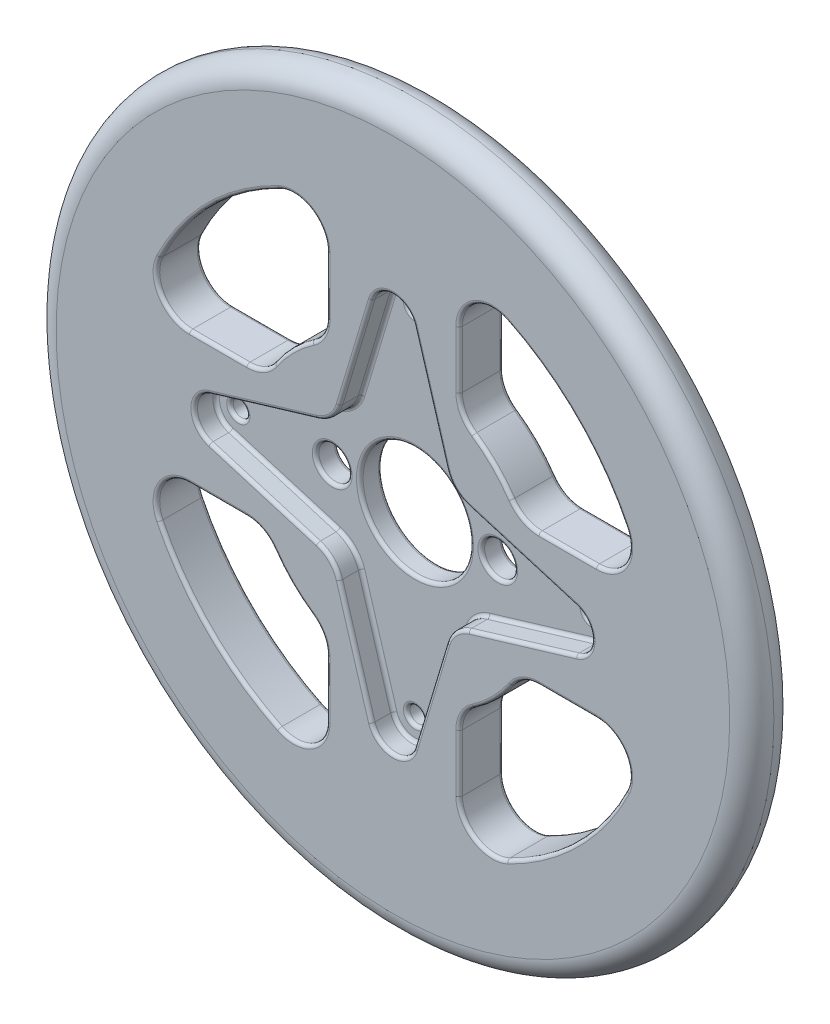
SolidWorks part; units mm, degrees
ref_plane "Front" through (0, 0, 0) normal (0, 0, 1) x (1, 0, 0)
ref_plane "Top" through (0, 0, 0) normal (0, 1, 0) x (1, 0, 0)
ref_plane "Right" through (0, 0, 0) normal (1, 0, 0) x (0, 0, -1)
sketch "Esquisse1" plane through (0, 0, 0) normal (0, 0, 1) x (1, 0, 0)
  circle A0 centre (0, 0) radius 32.5
  dimension "D1" = 65
extrude "Boss.-Extru.1" add sketch "Esquisse1" along normal blind 4
fillet "Congé1" radius 2 2 edges at (32.5, 0, 0) (32.5, 0, 4)
sketch "Esquisse2" plane through (0, 0, 4) normal (0, 0, 1) x (1, 0, 0)
  line L0 (-7.5, 0) -> (7.5, 0) construction
  circle A0 centre (-7.5, 0) radius 1.5
  circle A1 centre (7.5, 0) radius 1.5
  circle A2 centre (0, 0) radius 5
  point P5 (0, 0)
  dimension "D2" = 3
  dimension "D3" = 10
  dimension "D1" = 15
extrude "Enlèv. mat.-Extru.1" cut sketch "Esquisse2" against normal blind 4
sketch "Esquisse3" plane through (0, 0, 4) normal (0, 0, 1) x (1, 0, 0)
  line L0 (22.7211, 6) -> (11.5326, 6)
  line L1 (0, 0) -> (0, 30.5) construction
  line L2 (0, 0) -> (30.5, 0) construction
  line L3 (0, 0) -> (21.5668, 21.5668) construction
  line L4 (6, 22.7211) -> (6, 11.5326)
  circle A0 centre (0, 0) radius 23.5
  circle A1 centre (0, 0) radius 13
  circle A2 centre (0, 0) radius 30.5 construction
  point P14 (6, 11.5326)
  point P15 (6, 22.7211)
  dimension "D1" = 47
  dimension "D2" = 26
  dimension "D3" = 45
  dimension "D4" = 12
extrude "Enlèv. mat.-Extru.3" cut sketch "Esquisse3" against normal blind 4 contours A1 L0 A0 L4 region at (13.0471, 13.0471, 4)
fillet "Congé2" radius 3 4 edges at (22.7211, 6, 2) (6, 22.7211, 2) (11.5326, 6, 2) (6, 11.5326, 2)
pattern_circular "Répétition circulaire1" count 4 over 360 about axis through (0, 0, 4) along (0, 0, 1) of "Congé2", "Enlèv. mat.-Extru.3"
sketch "Esquisse4" plane through (0, 0, 4) normal (0, 0, 1) x (1, 0, 0)
  line L0 (0, 16) -> (0, 0) construction
  line L1 (-1.9154, 16.5757) -> (-5.3033, 5.3033)
  line L2 (1.9154, 16.5757) -> (5.3033, 5.3033)
  line L3 (0, 0) -> (30.5, 0) construction
  line L4 (0, 0) -> (11.3137, 11.3137) construction
  line L5 (-1.9154, -16.5757) -> (-5.3033, -5.3033)
  line L6 (1.9154, -16.5757) -> (5.3033, -5.3033)
  line L7 (16.5757, -1.9154) -> (5.3033, -5.3033)
  line L8 (16.5757, 1.9154) -> (5.3033, 5.3033)
  line L9 (-16.5757, 1.9154) -> (-5.3033, 5.3033)
  line L10 (-16.5757, -1.9154) -> (-5.3033, -5.3033)
  circle A0 centre (0, 16) radius 0.75
  circle A1 centre (0, -16) radius 0.75
  circle A2 centre (-16, 0) radius 0.75
  circle A3 centre (16, 0) radius 0.75
  circle A4 centre (0, 0) radius 16 construction
  circle A5 centre (0, 16) radius 2
  circle A6 centre (-16, 0) radius 2
  circle A7 centre (16, 0) radius 2
  circle A8 centre (0, -16) radius 2
  circle A9 centre (0, 0) radius 7.5 construction
  circle A10 centre (0, 0) radius 30.5 construction
  point P36 (-6.1441, 4.3011)
  circle M10 centre (7.5, 0) radius 1.5
  circle M11 centre (-7.5, 0) radius 1.5
  dimension "D1" = 32
  dimension "D2" = 1.5
  dimension "D3" = 4
  dimension "D4" = 15
  dimension "D5" = 45
extrude "Enlèv. mat.-Extru.4" cut sketch "Esquisse4" against normal blind 2 contours A8 L6 L7 A7 L8 L2 A5 L1 L9 A6 L10 L5 M11 M10 | A5 A0 | A6 A2 | A7 A3 | A8 A1 region at (0, 0, 4) region at (0, 17.9434, 4) region at (-14.8403, 1.5595, 4) region at (17.5595, 1.1597, 4) region at (-0.2827, -14.0772, 4)
sketch "Esquisse5" plane through (0, 0, 4) normal (0, 0, 1) x (1, 0, 0)
  circle A0 centre (-16, 0) radius 0.75
  circle A1 centre (0, 16) radius 0.75
  circle A2 centre (16, 0) radius 0.75
  circle A3 centre (0, -16) radius 0.75
  circle A4 centre (-16, 0) radius 0.75 construction
  circle A5 centre (0, 16) radius 0.75 construction
  circle A6 centre (0, -16) radius 0.75 construction
  circle A7 centre (16, 0) radius 0.75 construction
extrude "Enlèv. mat.-Extru.5" cut sketch "Esquisse5" against normal through all
fillet "Congé3" radius 3 4 edges at (-5.3033, 5.3033, 3) (-5.3033, -5.3033, 3) (5.3033, -5.3033, 3) (5.3033, 5.3033, 3)
fillet "Congé4" radius 0.3 110 edges at (0.75, -16, 2) (16.75, 0, 2) (0.75, 16, 2) (-15.25, 0, 2) (9, 0, 2) (-6, 0, 2) (5, 0, 2) (-5.5906, -5.5906, 2) (-11.7121, -3.3771, 2) (-18, 0, 2) (-11.7121, 3.3771, 2) (-5.5906, 5.5906, 2) (-3.3771, 11.7121, 2) (0, 18, 2) (3.3771, 11.7121, 2) (5.5906, 5.5906, 2) (11.7121, 3.3771, 2) (18, 0, 2) (11.7121, -3.3771, 2) (5.5906, -5.5906, 2) (3.3771, -11.7121, 2) (0, -18, 2) (-3.3771, -11.7121, 2) (-6.3483, -11.8256, 0) (-6, -15.8237, 0) (-7.4112, -20.9635, 0) (-16.617, -16.617, 0) (-20.9635, -7.4112, 0) (-15.8237, -6, 0) (-11.8256, -6.3483, 0) (-9.1924, -9.1924, 0) (-11.8256, 6.3483, 0) (-15.8237, 6, 0) (-20.9635, 7.4112, 0) (-16.617, 16.617, 0) (-7.4112, 20.9635, 0) (-6, 15.8237, 0) (-6.3483, 11.8256, 0) (-9.1924, 9.1924, 0) (-6, 0, 0) (5, 0, 0) (9, 0, 0) (6.3483, 11.8256, 0) (6, 15.8237, 0) (7.4112, 20.9635, 0) (16.617, 16.617, 0) (20.9635, 7.4112, 0) (15.8237, 6, 0) (11.8256, 6.3483, 0) (9.1924, 9.1924, 0) (11.8256, -6.3483, 0) (15.8237, -6, 0) (20.9635, -7.4112, 0) (16.617, -16.617, 0) (7.4112, -20.9635, 0) (6, -15.8237, 0) (6.3483, -11.8256, 0) (9.1924, -9.1924, 0) (-15.25, 0, 0) (0.75, -16, 0) (16.75, 0, 0) (0.75, 16, 0) (-18, 0, 4) (-11.7121, -3.3771, 4) (-5.5906, -5.5906, 4) (-3.3771, -11.7121, 4) (0, -18, 4) (3.3771, -11.7121, 4) (5.5906, -5.5906, 4) (11.7121, -3.3771, 4) (18, 0, 4) (11.7121, 3.3771, 4) (5.5906, 5.5906, 4) (3.3771, 11.7121, 4) (0, 18, 4) (-3.3771, 11.7121, 4) (-5.5906, 5.5906, 4) (-11.7121, 3.3771, 4) (7.4112, 20.9635, 4) (6, 15.8237, 4) (6.3483, 11.8256, 4) (9.1924, 9.1924, 4) (11.8256, 6.3483, 4) (15.8237, 6, 4) (20.9635, 7.4112, 4) (16.617, 16.617, 4) (-20.9635, 7.4112, 4) (-15.8237, 6, 4) (-11.8256, 6.3483, 4) (-9.1924, 9.1924, 4) (-6.3483, 11.8256, 4) (-6, 15.8237, 4) (-7.4112, 20.9635, 4) (-16.617, 16.617, 4) (20.9635, -7.4112, 4) (15.8237, -6, 4) (11.8256, -6.3483, 4) (9.1924, -9.1924, 4) (6.3483, -11.8256, 4) (6, -15.8237, 4) (7.4112, -20.9635, 4) (16.617, -16.617, 4) (-7.4112, -20.9635, 4) (-6, -15.8237, 4) (-6.3483, -11.8256, 4) (-9.1924, -9.1924, 4) (-11.8256, -6.3483, 4) (-15.8237, -6, 4) (-20.9635, -7.4112, 4) (-16.617, -16.617, 4)
